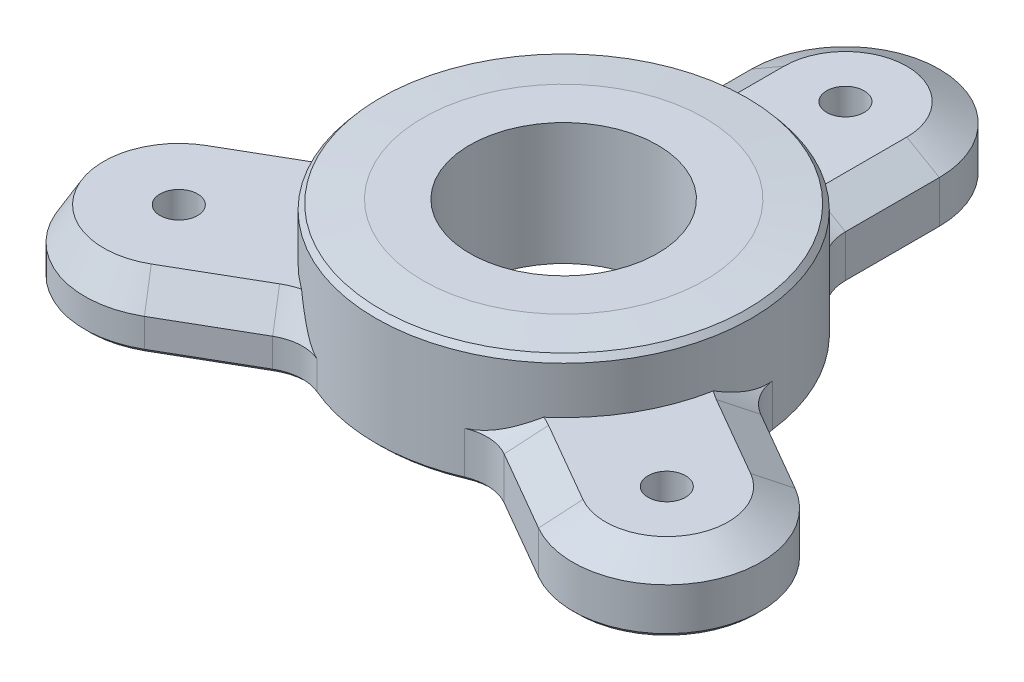
SolidWorks part; units mm, degrees
material "ﾒﾗﾐﾝ樹脂"
ref_plane "正面" through (0, 0, 0) normal (0, 0, 1) x (1, 0, 0)
ref_plane "平面" through (0, 0, 0) normal (0, 1, 0) x (1, 0, 0)
ref_plane "右側面" through (0, 0, 0) normal (1, 0, 0) x (0, 0, -1)
sketch "ｽｹｯﾁ2" plane through (0, 0, 0) normal (0, 1, 0) x (1, 0, 0)
  line L0 (20.9808, -23.6603) -> (10, -17.3205)
  line L1 (30.9808, -6.3397) -> (20, 0)
  line L2 (10, 30) -> (10, 17.3205)
  line L3 (-10, 30) -> (-10, 17.3205)
  line L4 (-30.9808, -6.3397) -> (-20, 0)
  line L5 (-20.9808, -23.6603) -> (-10, -17.3205)
  circle A0 centre (0, 0) radius 20
  circle A1 centre (0, 0) radius 10
  circle A2 centre (0, 30) radius 2
  circle A3 centre (25.9808, -15) radius 2
  circle A4 centre (-25.9808, -15) radius 2
  arc A5 (-10, 30) -> (10, 30) centre (0, 30) cw
  arc A6 (30.9808, -6.3397) -> (20.9808, -23.6603) centre (25.9808, -15) cw
  arc A7 (-20.9808, -23.6603) -> (-30.9808, -6.3397) centre (-25.9808, -15) cw
  point P12 (0, 0)
  point P28 (0, 0)
  dimension "D1" = 3
  dimension "D2" = 3
extrude "ﾎﾞｽ - 押し出し1" add sketch "ｽｹｯﾁ2" along normal blind 7 contours A6 L1 A0 L0 A3 | A7 L5 A0 L4 A4 | A5 L3 A0 L2 A2 region at (15.6707, 0, 20.1781) region at (-15.6707, 0, 20.1781) region at (0, 0, -20.3024)
sketch "ｽｹｯﾁ3" plane through (0, 0, 0) normal (0, -1, 0) x (1, 0, 0)
  circle A0 centre (0, 0) radius 20
  circle A1 centre (0, 0) radius 10
extrude "ﾎﾞｽ - 押し出し2" add sketch "ｽｹｯﾁ3" against normal blind 13
fillet "ﾌｨﾚｯﾄ1" radius 5 6 edges at (-10, 3.5, -17.3205) (-20, 3.5, 0) (-10, 3.5, 17.3205) (10, 3.5, 17.3205) (20, 3.5, 0) (10, 3.5, -17.3205)
chamfer "面取り1" distance 5 angle 5 1 edges at (0, 13, -20) first distance on face at (0, 13, -10)
chamfer "面取り2" distance 2 angle 60 15 edges at (10.1201, 7, 17.9994) (16.6506, 7, 21.1603) (34.641, 7, 20) (26.6506, 7, 3.8397) (20.6479, 7, -0.2354) (10.5279, 7, -17.7639) (10, 7, -25) (0, 7, -40) (-10, 7, -25) (-10.5279, 7, -17.7639) (-20.6479, 7, -0.2354) (-26.6506, 7, 3.8397) (-10.1201, 7, 17.9994) (-16.6506, 7, 21.1603) (-34.641, 7, 20) first distance on face at (10.1043, 3.5, 18.2628) first distance on face at (16.6506, 3.5, 21.1603) first distance on face at (30.3109, 3.5, 17.5) first distance on face at (26.6506, 3.5, 3.8397) first distance on face at (20.8682, 3.5, -0.3809) first distance on face at (10.7639, 3.5, -17.882) first distance on face at (10, 3.5, -25) first distance on face at (0, 3.5, -35) first distance on face at (-10, 3.5, -25) first distance on face at (-10.7639, 3.5, -17.882) first distance on face at (-21.0051, 7, 12.1273)
chamfer "面取り3" distance 0.5 angle 45 18 edges at (34.641, 0, 20) (16.6506, 0, 21.1603) (10.1201, 0, 17.9994) (0, 0, 20) (-10.1201, 0, 17.9994) (-16.6506, 0, 21.1603) (-34.641, 0, 20) (-26.6506, 0, 3.8397) (-20.6479, 0, -0.2354) (-17.3205, 0, -10) (-10.5279, 0, -17.7639) (-10, 0, -25) (0, 0, -40) (10, 0, -25) (10.5279, 0, -17.7639) (17.3205, 0, -10) (26.6506, 0, 3.8397) (20.6479, 0, -0.2354)
chamfer "面取り4" distance 0.5 angle 45 1 edges at (0, 12.5626, -20) first distance on face at (0, 13, -15)
